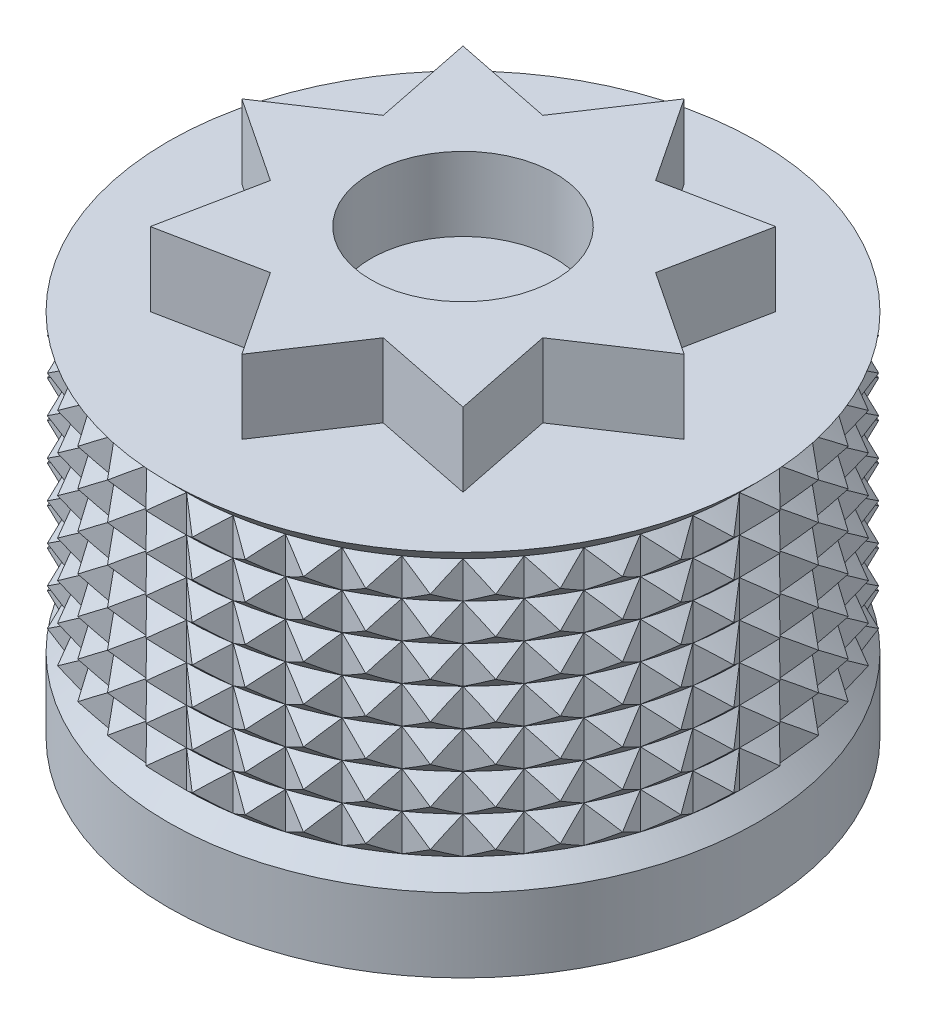
SolidWorks part; units mm, degrees
ref_plane "Front Plane" through (0, 0, 0) normal (0, 0, 1) x (1, 0, 0)
ref_plane "Top Plane" through (0, 0, 0) normal (0, 1, 0) x (1, 0, 0)
ref_plane "Right Plane" through (0, 0, 0) normal (1, 0, 0) x (0, 0, -1)
sketch "Sketch2" plane through (0, 0, 0) normal (0, 0, 1) x (1, 0, 0)
  line L0 (0, 0) -> (0, 12)
  line L1 (0, 0) -> (8, 0)
  line L2 (8, 0) -> (8, 2)
  line L3 (8, 2) -> (7.5, 2.5)
  line L4 (7.5, 2.5) -> (8, 3)
  line L5 (7.5, 3.5) -> (8, 4)
  line L6 (8, 3) -> (7.5, 3.5)
  line L7 (7.5, 4.5) -> (8, 5)
  line L8 (8, 4) -> (7.5, 4.5)
  line L9 (7.5, 5.5) -> (8, 6)
  line L10 (8, 5) -> (7.5, 5.5)
  line L11 (7.5, 6.5) -> (8, 7)
  line L12 (8, 6) -> (7.5, 6.5)
  line L13 (7.5, 7.5) -> (8, 8)
  line L14 (8, 7) -> (7.5, 7.5)
  line L15 (7.5, 8.5) -> (8, 9)
  line L16 (8, 8) -> (7.5, 8.5)
  line L17 (7.5, 9.5) -> (8, 10)
  line L18 (8, 9) -> (7.5, 9.5)
  line L29 (0, 12) -> (7, 12)
  line L30 (8, 11) -> (8, 10)
  arc A0 (7, 12) -> (8, 11) centre (7, 11) cw
  dimension "D7" = 1
  dimension "D1" = 12
  dimension "D2" = 8
  dimension "D3" = 2
  dimension "D4" = 135
  dimension "D5" = 0.5
  dimension "D6" = 8
revolve "Revolve1" add sketch "Sketch2" angle 360 about L0
ref_plane "Plane1" through (0, 9.5, 0) normal (0, 1, 0) x (1, 0, 0)
ref_plane "Plane2" through (0, 2.5, 0) normal (0, 1, 0) x (1, 0, 0)
sketch "Sketch3" plane through (0, 9.5, 0) normal (0, 1, 0) x (1, 0, 0)
  line L0 (0, 0) -> (0, 8.5914) construction
  line L1 (0, 0) -> (0.7361, 9.3536) construction
  line L2 (0, 7.5) -> (0.6277, 7.9753)
  line L3 (0.6277, 7.9753) -> (1.1733, 7.4077)
  line L4 (0, 0) -> (1.5352, 9.6931) construction
  line L5 (1.1733, 7.4077) -> (1.8676, 7.779)
  line L6 (1.8676, 7.779) -> (2.3176, 7.1329)
  line L7 (2.3176, 7.1329) -> (3.0615, 7.391)
  line L8 (3.0615, 7.391) -> (3.4049, 6.6825)
  line L9 (3.4049, 6.6825) -> (4.18, 6.8211)
  line L10 (4.18, 6.8211) -> (4.4084, 6.0676)
  line L11 (4.4084, 6.0676) -> (5.1956, 6.0832)
  line L12 (5.1956, 6.0832) -> (5.3033, 5.3033)
  line L13 (5.3033, 5.3033) -> (6.0832, 5.1956)
  line L14 (6.0832, 5.1956) -> (6.0676, 4.4084)
  line L15 (6.0676, 4.4084) -> (6.8211, 4.18)
  line L16 (6.8211, 4.18) -> (6.6825, 3.4049)
  line L17 (6.6825, 3.4049) -> (7.391, 3.0615)
  line L18 (7.391, 3.0615) -> (7.1329, 2.3176)
  line L19 (7.1329, 2.3176) -> (7.779, 1.8676)
  line L20 (7.779, 1.8676) -> (7.4077, 1.1733)
  line L21 (7.4077, 1.1733) -> (7.9753, 0.6277)
  line L22 (7.9753, 0.6277) -> (7.5, 0)
  line L23 (7.5, 0) -> (7.9753, -0.6277)
  line L24 (7.9753, -0.6277) -> (7.4077, -1.1733)
  line L25 (7.4077, -1.1733) -> (7.779, -1.8676)
  line L26 (7.779, -1.8676) -> (7.1329, -2.3176)
  line L27 (7.1329, -2.3176) -> (7.391, -3.0615)
  line L28 (7.391, -3.0615) -> (6.6825, -3.4049)
  line L29 (6.6825, -3.4049) -> (6.8211, -4.18)
  line L30 (6.8211, -4.18) -> (6.0676, -4.4084)
  line L31 (6.0676, -4.4084) -> (6.0832, -5.1956)
  line L32 (6.0832, -5.1956) -> (5.3033, -5.3033)
  line L33 (5.3033, -5.3033) -> (5.1956, -6.0832)
  line L34 (5.1956, -6.0832) -> (4.4084, -6.0676)
  line L35 (4.4084, -6.0676) -> (4.18, -6.8211)
  line L36 (4.18, -6.8211) -> (3.4049, -6.6825)
  line L37 (3.4049, -6.6825) -> (3.0615, -7.391)
  line L38 (3.0615, -7.391) -> (2.3176, -7.1329)
  line L39 (2.3176, -7.1329) -> (1.8676, -7.779)
  line L40 (1.8676, -7.779) -> (1.1733, -7.4077)
  line L41 (1.1733, -7.4077) -> (0.6277, -7.9753)
  line L42 (0.6277, -7.9753) -> (0, -7.5)
  line L43 (0, -7.5) -> (-0.6277, -7.9753)
  line L44 (-0.6277, -7.9753) -> (-1.1733, -7.4077)
  line L45 (-1.1733, -7.4077) -> (-1.8676, -7.779)
  line L46 (-1.8676, -7.779) -> (-2.3176, -7.1329)
  line L47 (-2.3176, -7.1329) -> (-3.0615, -7.391)
  line L48 (-3.0615, -7.391) -> (-3.4049, -6.6825)
  line L49 (-3.4049, -6.6825) -> (-4.18, -6.8211)
  line L50 (-4.18, -6.8211) -> (-4.4084, -6.0676)
  line L51 (-4.4084, -6.0676) -> (-5.1956, -6.0832)
  line L52 (-5.1956, -6.0832) -> (-5.3033, -5.3033)
  line L53 (-5.3033, -5.3033) -> (-6.0832, -5.1956)
  line L54 (-6.0832, -5.1956) -> (-6.0676, -4.4084)
  line L55 (-6.0676, -4.4084) -> (-6.8211, -4.18)
  line L56 (-6.8211, -4.18) -> (-6.6825, -3.4049)
  line L57 (-6.6825, -3.4049) -> (-7.391, -3.0615)
  line L58 (-7.391, -3.0615) -> (-7.1329, -2.3176)
  line L59 (-7.1329, -2.3176) -> (-7.779, -1.8676)
  line L60 (-7.779, -1.8676) -> (-7.4077, -1.1733)
  line L61 (-7.4077, -1.1733) -> (-7.9753, -0.6277)
  line L62 (-7.9753, -0.6277) -> (-7.5, 0)
  line L63 (-7.5, 0) -> (-7.9753, 0.6277)
  line L64 (-7.9753, 0.6277) -> (-7.4077, 1.1733)
  line L65 (-7.4077, 1.1733) -> (-7.779, 1.8676)
  line L66 (-7.779, 1.8676) -> (-7.1329, 2.3176)
  line L67 (-7.1329, 2.3176) -> (-7.391, 3.0615)
  line L68 (-7.391, 3.0615) -> (-6.6825, 3.4049)
  line L69 (-6.6825, 3.4049) -> (-6.8211, 4.18)
  line L70 (-6.8211, 4.18) -> (-6.0676, 4.4084)
  line L71 (-6.0676, 4.4084) -> (-6.0832, 5.1956)
  line L72 (-6.0832, 5.1956) -> (-5.3033, 5.3033)
  line L73 (-5.3033, 5.3033) -> (-5.1956, 6.0832)
  line L74 (-5.1956, 6.0832) -> (-4.4084, 6.0676)
  line L75 (-4.4084, 6.0676) -> (-4.18, 6.8211)
  line L76 (-4.18, 6.8211) -> (-3.4049, 6.6825)
  line L77 (-3.4049, 6.6825) -> (-3.0615, 7.391)
  line L78 (-3.0615, 7.391) -> (-2.3176, 7.1329)
  line L79 (-2.3176, 7.1329) -> (-1.8676, 7.779)
  line L80 (-1.8676, 7.779) -> (-1.1733, 7.4077)
  line L81 (-1.1733, 7.4077) -> (-0.6277, 7.9753)
  line L82 (-0.6277, 7.9753) -> (0, 7.5)
  circle A0 centre (0, 0) radius 7.5 construction
  circle A1 centre (0, 0) radius 8 construction
  point P130 (0, 0)
  dimension "D2" = 0.5
  dimension "D1" = 4.5
  dimension "D3" = 4.5
  dimension "D4" = 40
extrude "Cut-Extrude2" cut sketch "Sketch3" against normal up to surface (7 mm away) flip side to cut up to plane "Plane2"
sketch "Sketch5" plane through (0, 0, 0) normal (0, -1, 0) x (1, 0, 0)
  circle A0 centre (0, 0) radius 7
  circle A1 centre (0, 0) radius 8 construction
  dimension "D1" = 1
extrude "Cut-Extrude4" cut sketch "Sketch5" against normal blind 1
sketch "Sketch4" plane through (0, 1, 0) normal (0, -1, 0) x (1, 0, 0)
  line L0 (-2.5981, 1.5) -> (2.5981, 1.5) construction
  line L1 (-2.7111, 1.7) -> (2.7111, 1.7)
  arc A0 (2.5981, 1.5) -> (-2.5981, 1.5) centre (0, 0) cw construction
  arc A1 (2.7111, 1.7) -> (-2.7111, 1.7) centre (0, 0) cw
  dimension "D1" = 3
  dimension "D2" = 1.5
  dimension "D3" = 0.2
extrude "Cut-Extrude3" cut sketch "Sketch4" against normal blind 8
sketch "Sketch6" plane through (0, 1, 0) normal (0, -1, 0) x (1, 0, 0)
  line L0 (-2.4, 1.7) -> (-2.2, 1.35)
  line L1 (-2.2, 1.35) -> (-2, 1.7)
  line L2 (-2.4, 1.7) -> (-2, 1.7)
  line L3 (2.7111, 1.7) -> (-2.7111, 1.7) construction
  line L4 (0, 0) -> (0, 3.2663) construction
  line L5 (-3.2, 0.2) -> (-3.2, -0.2)
  line L6 (0, 0) -> (-3.6545, 0) construction
  line L7 (-3.2, 0.2) -> (-2.85, 0)
  line L8 (-2.85, 0) -> (-3.2, -0.2)
  line L9 (-2.9699, -1.2082) -> (-2.7963, -1.5686)
  line L10 (-2.9699, -1.2082) -> (-2.5678, -1.2366)
  line L11 (-2.5678, -1.2366) -> (-2.7963, -1.5686)
  line L12 (-2.1515, -2.3772) -> (-1.8388, -2.6266)
  line L13 (-2.1515, -2.3772) -> (-1.7769, -2.2282)
  line L14 (-1.7769, -2.2282) -> (-1.8388, -2.6266)
  line L15 (-0.9071, -3.0753) -> (-0.5171, -3.1643)
  line L16 (-0.9071, -3.0753) -> (-0.6342, -2.7785)
  line L17 (-0.6342, -2.7785) -> (-0.5171, -3.1643)
  line L18 (0.5171, -3.1643) -> (0.9071, -3.0753)
  line L19 (0.5171, -3.1643) -> (0.6342, -2.7785)
  line L20 (0.6342, -2.7785) -> (0.9071, -3.0753)
  line L21 (1.8388, -2.6266) -> (2.1515, -2.3772)
  line L22 (1.8388, -2.6266) -> (1.7769, -2.2282)
  line L23 (1.7769, -2.2282) -> (2.1515, -2.3772)
  line L24 (2.7963, -1.5686) -> (2.9699, -1.2082)
  line L25 (2.7963, -1.5686) -> (2.5678, -1.2366)
  line L26 (2.5678, -1.2366) -> (2.9699, -1.2082)
  line L27 (3.2, -0.2) -> (3.2, 0.2)
  line L28 (3.2, -0.2) -> (2.85, 0)
  line L29 (2.85, 0) -> (3.2, 0.2)
  line L30 (-1.3, 1.7) -> (-1.1, 1.35)
  line L31 (-1.1, 1.35) -> (-0.9, 1.7)
  line L32 (-1.3, 1.7) -> (-0.9, 1.7)
  line L33 (-0.2, 1.7) -> (0, 1.35)
  line L34 (0, 1.35) -> (0.2, 1.7)
  line L35 (-0.2, 1.7) -> (0.2, 1.7)
  line L36 (0.9, 1.7) -> (1.1, 1.35)
  line L37 (1.1, 1.35) -> (1.3, 1.7)
  line L38 (0.9, 1.7) -> (1.3, 1.7)
  line L39 (2, 1.7) -> (2.2, 1.35)
  line L40 (2.2, 1.35) -> (2.4, 1.7)
  line L41 (2, 1.7) -> (2.4, 1.7)
  arc A0 (-2.7111, 1.7) -> (2.7111, 1.7) centre (0, 0) ccw construction
  arc A1 (-2.7111, 1.7) -> (2.7111, 1.7) centre (0, 0) ccw construction
  point P5 (-2.2, 1.7)
  point P17 (-3.2, 0)
  point P44 (0, 0)
  dimension "D1" = 0.4
  dimension "D2" = 0.35
  dimension "D3" = 2
  dimension "D4" = 90
  dimension "D5" = 0.4
  dimension "D6" = 0.35
  dimension "D8" = 5
  dimension "D7" = 8
extrude "Boss-Extrude2" add sketch "Sketch6" against normal up to surface (8 mm away) up to face at (0, 9, -0.75)
sketch "Sketch7" plane through (0, 12, 0) normal (0, 1, 0) x (1, 0, 0)
  line L0 (0, 0) -> (0, 8.9713) construction
  line L1 (0, 0) -> (3.4051, 8.2205) construction
  line L2 (0, 0) -> (-3.5263, 8.5132) construction
  line L3 (-1.5307, 3.6955) -> (0, 6)
  line L4 (0, 6) -> (1.5307, 3.6955)
  line L5 (1.5307, 3.6955) -> (4.2426, 4.2426)
  line L6 (4.2426, 4.2426) -> (3.6955, 1.5307)
  line L7 (3.6955, 1.5307) -> (6, 0)
  line L8 (6, 0) -> (3.6955, -1.5307)
  line L9 (3.6955, -1.5307) -> (4.2426, -4.2426)
  line L10 (4.2426, -4.2426) -> (1.5307, -3.6955)
  line L11 (1.5307, -3.6955) -> (0, -6)
  line L12 (0, -6) -> (-1.5307, -3.6955)
  line L13 (-1.5307, -3.6955) -> (-4.2426, -4.2426)
  line L14 (-4.2426, -4.2426) -> (-3.6955, -1.5307)
  line L15 (-3.6955, -1.5307) -> (-6, 0)
  line L16 (-6, 0) -> (-3.6955, 1.5307)
  line L17 (-3.6955, 1.5307) -> (-4.2426, 4.2426)
  line L18 (-4.2426, 4.2426) -> (-1.5307, 3.6955)
  circle A0 centre (0, 0) radius 2.5
  circle A1 centre (0, 0) radius 4 construction
  circle A2 centre (0, 0) radius 6 construction
  point P34 (0, 0)
  dimension "D1" = 5
  dimension "D2" = 8
  dimension "D3" = 12
  dimension "D4" = 22.5
  dimension "D5" = 22.5
  dimension "D6" = 8
extrude "Cut-Extrude5" cut sketch "Sketch7" against normal blind 2 flip side to cut
sketch "Sketch11" plane through (0, 1, 0) normal (0, -1, 0) x (1, 0, 0)
  line L0 (-2.7111, 1.7) -> (2.7111, 1.7)
  arc A0 (-2.7111, 1.7) -> (2.7111, 1.7) centre (0, 0) ccw
  arc A1 (3.194, 0.1965) -> (2.7111, 1.7) centre (0, 0) ccw construction
extrude "Cut-Extrude7" cut sketch "Sketch11" against normal blind 5 draft 15
